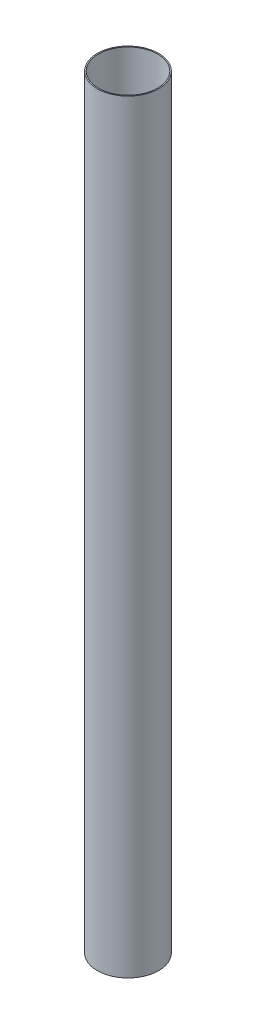
SolidWorks part; units mm, degrees
ref_plane "Front Plane" through (0, 0, 0) normal (0, 0, 1) x (1, 0, 0)
ref_plane "Top Plane" through (0, 0, 0) normal (0, 1, 0) x (1, 0, 0)
ref_plane "Right Plane" through (0, 0, 0) normal (1, 0, 0) x (0, 0, -1)
sketch "Sketch1" plane through (0, 0, 0) normal (0, 1, 0) x (1, 0, 0)
  circle A0 centre (0, 0) radius 39.5
  circle A1 centre (0, 0) radius 41
  dimension "D1" = 82
  dimension "D2" = 79
extrude "Boss-Extrude1" add sketch "Sketch1" along normal blind 1020
